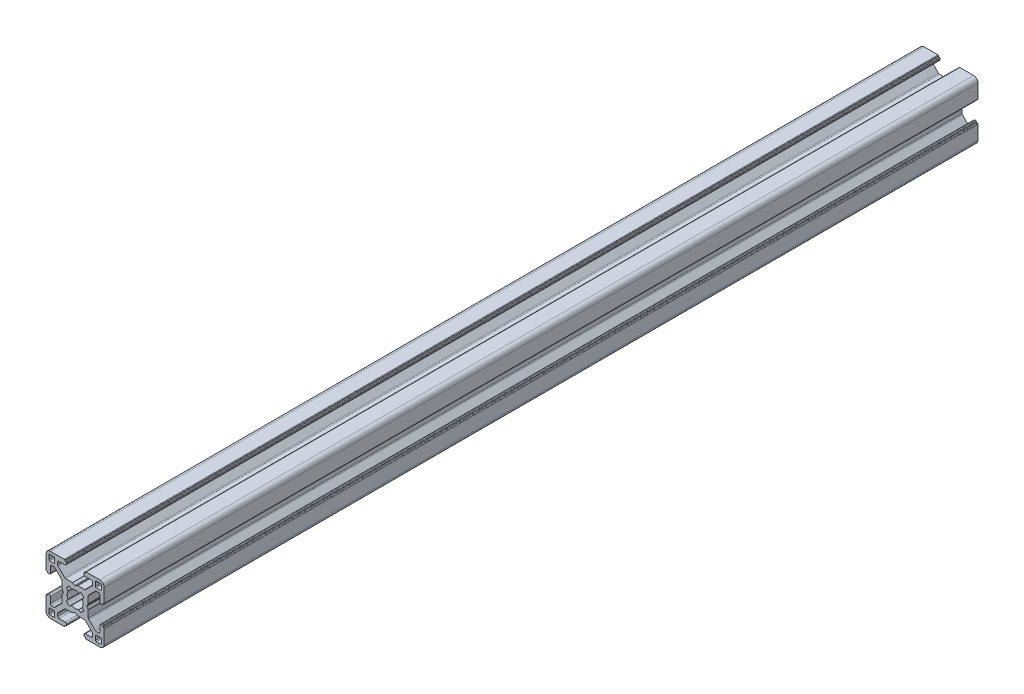
SolidWorks part; units mm, degrees
material "6063-O, Barra estrusa (SS)"
ref_plane "Piano frontale" through (0, 0, 0) normal (0, 0, 1) x (1, 0, 0)
ref_plane "Piano superiore" through (0, 0, 0) normal (0, 1, 0) x (1, 0, 0)
ref_plane "Piano destro" through (0, 0, 0) normal (1, 0, 0) x (0, 0, -1)
ref_plane "Piano1" through (0, 0, 100) normal (0, 0, 1) x (1, 0, 0)
sketch "Schizzo1" plane through (0, 0, 100) normal (0, 0, 1) x (1, 0, 0)
  line L0 (-1.9139, 2.9896) -> (-1.2582, 2.4453)
  line L1 (1.2582, 2.4453) -> (1.9139, 2.9896)
  line L2 (2.9922, 1.9099) -> (2.4453, 1.2582)
  line L3 (2.4453, -1.2582) -> (2.9922, -1.9099)
  line L4 (1.9139, -2.9896) -> (1.2582, -2.4453)
  line L5 (-1.2582, -2.4453) -> (-1.9139, -2.9896)
  line L6 (-2.9922, -1.9099) -> (-2.4453, -1.2582)
  line L7 (-2.4453, 1.2582) -> (-2.9922, 1.9099)
  line L8 (-9.3, 3) -> (-9, 3)
  line L9 (-8.5, 3.5) -> (-8.5, 5.5)
  line L10 (-8, 6) -> (-7.2678, 6)
  line L11 (-6.9142, 5.8536) -> (-4.6464, 3.5858)
  line L12 (-4.5, 3.2322) -> (-4.5, 0.9536)
  line L13 (-4.4732, 0.8536) -> (-4.0381, 0.1)
  line L14 (-4.0381, -0.1) -> (-4.4732, -0.8536)
  line L15 (-4.5, -0.9536) -> (-4.5, -3.2322)
  line L16 (-4.6464, -3.5858) -> (-6.9142, -5.8536)
  line L17 (-7.2678, -6) -> (-8, -6)
  line L18 (-8.5, -5.5) -> (-8.5, -3.5)
  line L19 (-9, -3) -> (-9.3, -3)
  line L20 (-9.5, -3.2) -> (-9.5, -3.35)
  line L21 (-9.7, -3.55) -> (-9.8, -3.55)
  line L22 (-10, -3.75) -> (-10, -8.5)
  line L23 (-8.5, -10) -> (-3.75, -10)
  line L24 (-3.55, -9.8) -> (-3.55, -9.7)
  line L25 (-3.35, -9.5) -> (-3.2, -9.5)
  line L26 (-3, -9.3) -> (-3, -9)
  line L27 (-3.5, -8.5) -> (-5.5, -8.5)
  line L28 (-6, -8) -> (-6, -7.2678)
  line L29 (-5.8536, -6.9142) -> (-3.5858, -4.6464)
  line L30 (-3.2322, -4.5) -> (-0.9536, -4.5)
  line L31 (-0.8536, -4.4732) -> (-0.1, -4.0381)
  line L32 (0.1, -4.0381) -> (0.8536, -4.4732)
  line L33 (0.9536, -4.5) -> (3.2322, -4.5)
  line L34 (3.5858, -4.6464) -> (5.8536, -6.9142)
  line L35 (6, -7.2678) -> (6, -8)
  line L36 (5.5, -8.5) -> (3.5, -8.5)
  line L37 (3, -9) -> (3, -9.3)
  line L38 (3.2, -9.5) -> (3.35, -9.5)
  line L39 (3.55, -9.7) -> (3.55, -9.8)
  line L40 (3.75, -10) -> (8.5, -10)
  line L41 (10, -8.5) -> (10, -3.75)
  line L42 (9.8, -3.55) -> (9.7, -3.55)
  line L43 (9.5, -3.35) -> (9.5, -3.2)
  line L44 (9.3, -3) -> (9, -3)
  line L45 (8.5, -3.5) -> (8.5, -5.5)
  line L46 (8, -6) -> (7.2678, -6)
  line L47 (6.9142, -5.8536) -> (4.6464, -3.5858)
  line L48 (4.5, -3.2322) -> (4.5, -0.9536)
  line L49 (4.4732, -0.8536) -> (4.0381, -0.1)
  line L50 (4.0381, 0.1) -> (4.4732, 0.8536)
  line L51 (4.5, 0.9536) -> (4.5, 3.2322)
  line L52 (4.6464, 3.5858) -> (6.9142, 5.8536)
  line L53 (7.2678, 6) -> (8, 6)
  line L54 (8.5, 5.5) -> (8.5, 3.5)
  line L55 (9, 3) -> (9.3, 3)
  line L56 (9.5, 3.2) -> (9.5, 3.35)
  line L57 (9.7, 3.55) -> (9.8, 3.55)
  line L58 (10, 3.75) -> (10, 8.5)
  line L59 (8.5, 10) -> (3.75, 10)
  line L60 (3.55, 9.8) -> (3.55, 9.7)
  line L61 (3.35, 9.5) -> (3.2, 9.5)
  line L62 (3, 9.3) -> (3, 9)
  line L63 (3.5, 8.5) -> (5.5, 8.5)
  line L64 (6, 8) -> (6, 7.2678)
  line L65 (5.8536, 6.9142) -> (3.5858, 4.6464)
  line L66 (3.2322, 4.5) -> (0.9536, 4.5)
  line L67 (0.8536, 4.4732) -> (0.1, 4.0381)
  line L68 (-0.1, 4.0381) -> (-0.8536, 4.4732)
  line L69 (-0.9536, 4.5) -> (-3.2322, 4.5)
  line L70 (-3.5858, 4.6464) -> (-5.8536, 6.9142)
  line L71 (-6, 7.2678) -> (-6, 8)
  line L72 (-5.5, 8.5) -> (-3.5, 8.5)
  line L73 (-3, 9) -> (-3, 9.3)
  line L74 (-3.2, 9.5) -> (-3.35, 9.5)
  line L75 (-3.55, 9.7) -> (-3.55, 9.8)
  line L76 (-3.75, 10) -> (-8.5, 10)
  line L77 (-10, 8.5) -> (-10, 3.75)
  line L78 (-9.8, 3.55) -> (-9.7, 3.55)
  line L79 (-9.5, 3.35) -> (-9.5, 3.2)
  line L80 (8.7, 7) -> (7.3, 7)
  line L81 (-7.3, 7) -> (-8.7, 7)
  line L82 (-7, 7.3) -> (-7, 8.7)
  line L83 (-7.3, 9) -> (-8.7, 9)
  line L84 (-9, 7.3) -> (-9, 8.7)
  line L85 (9, 7.3) -> (9, 8.7)
  line L86 (8.7, 9) -> (7.3, 9)
  line L87 (7, 7.3) -> (7, 8.7)
  line L88 (8.7, -9) -> (7.3, -9)
  line L89 (9, -8.7) -> (9, -7.3)
  line L90 (8.7, -7) -> (7.3, -7)
  line L91 (7, -8.7) -> (7, -7.3)
  line L92 (-7.3, -9) -> (-8.7, -9)
  line L93 (-7, -8.7) -> (-7, -7.3)
  line L94 (-7.3, -7) -> (-8.7, -7)
  line L95 (-9, -8.7) -> (-9, -7.3)
  arc A0 (-1.2582, 2.4453) -> (1.2582, 2.4453) centre (0, 0) cw
  arc A1 (1.9139, 2.9896) -> (2.9922, 1.9099) centre (0, 0) cw
  arc A2 (2.4453, 1.2582) -> (2.4453, -1.2582) centre (0, 0) cw
  arc A3 (2.9922, -1.9099) -> (1.9139, -2.9896) centre (0, 0) cw
  arc A4 (1.2582, -2.4453) -> (-1.2582, -2.4453) centre (0, 0) cw
  arc A5 (-1.9139, -2.9896) -> (-2.9922, -1.9099) centre (0, 0) cw
  arc A6 (-2.4453, -1.2582) -> (-2.4453, 1.2582) centre (0, 0) cw
  arc A7 (-2.9922, 1.9099) -> (-1.9139, 2.9896) centre (0, 0) cw
  arc A8 (-9.5, 3.2) -> (-9.3, 3) centre (-9.3, 3.2) ccw
  arc A9 (-9, 3) -> (-8.5, 3.5) centre (-9, 3.5) ccw
  arc A10 (-8.5, 5.5) -> (-8, 6) centre (-8, 5.5) cw
  arc A11 (-7.2678, 6) -> (-6.9142, 5.8536) centre (-7.2678, 5.5) cw
  arc A12 (-4.6464, 3.5858) -> (-4.5, 3.2322) centre (-5, 3.2322) cw
  arc A13 (-4.5, 0.9536) -> (-4.4732, 0.8536) centre (-4.3, 0.9536) ccw
  arc A14 (-4.0381, 0.1) -> (-4.0381, -0.1) centre (-4.2113, 0) cw
  arc A15 (-4.4732, -0.8536) -> (-4.5, -0.9536) centre (-4.3, -0.9536) ccw
  arc A16 (-4.5, -3.2322) -> (-4.6464, -3.5858) centre (-5, -3.2322) cw
  arc A17 (-6.9142, -5.8536) -> (-7.2678, -6) centre (-7.2678, -5.5) cw
  arc A18 (-8, -6) -> (-8.5, -5.5) centre (-8, -5.5) cw
  arc A19 (-8.5, -3.5) -> (-9, -3) centre (-9, -3.5) ccw
  arc A20 (-9.3, -3) -> (-9.5, -3.2) centre (-9.3, -3.2) ccw
  arc A21 (-9.5, -3.35) -> (-9.7, -3.55) centre (-9.7, -3.35) cw
  arc A22 (-9.8, -3.55) -> (-10, -3.75) centre (-9.8, -3.75) ccw
  arc A23 (-10, -8.5) -> (-8.5, -10) centre (-8.5, -8.5) ccw
  arc A24 (-3.75, -10) -> (-3.55, -9.8) centre (-3.75, -9.8) ccw
  arc A25 (-3.55, -9.7) -> (-3.35, -9.5) centre (-3.35, -9.7) cw
  arc A26 (-3.2, -9.5) -> (-3, -9.3) centre (-3.2, -9.3) ccw
  arc A27 (-3, -9) -> (-3.5, -8.5) centre (-3.5, -9) ccw
  arc A28 (-5.5, -8.5) -> (-6, -8) centre (-5.5, -8) cw
  arc A29 (-6, -7.2678) -> (-5.8536, -6.9142) centre (-5.5, -7.2678) cw
  arc A30 (-3.5858, -4.6464) -> (-3.2322, -4.5) centre (-3.2322, -5) cw
  arc A31 (-0.9536, -4.5) -> (-0.8536, -4.4732) centre (-0.9536, -4.3) ccw
  arc A32 (-0.1, -4.0381) -> (0.1, -4.0381) centre (0, -4.2113) cw
  arc A33 (0.8536, -4.4732) -> (0.9536, -4.5) centre (0.9536, -4.3) ccw
  arc A34 (3.2322, -4.5) -> (3.5858, -4.6464) centre (3.2322, -5) cw
  arc A35 (5.8536, -6.9142) -> (6, -7.2678) centre (5.5, -7.2678) cw
  arc A36 (6, -8) -> (5.5, -8.5) centre (5.5, -8) cw
  arc A37 (3.5, -8.5) -> (3, -9) centre (3.5, -9) ccw
  arc A38 (3, -9.3) -> (3.2, -9.5) centre (3.2, -9.3) ccw
  arc A39 (3.35, -9.5) -> (3.55, -9.7) centre (3.35, -9.7) cw
  arc A40 (3.55, -9.8) -> (3.75, -10) centre (3.75, -9.8) ccw
  arc A41 (8.5, -10) -> (10, -8.5) centre (8.5, -8.5) ccw
  arc A42 (10, -3.75) -> (9.8, -3.55) centre (9.8, -3.75) ccw
  arc A43 (9.7, -3.55) -> (9.5, -3.35) centre (9.7, -3.35) cw
  arc A44 (9.5, -3.2) -> (9.3, -3) centre (9.3, -3.2) ccw
  arc A45 (9, -3) -> (8.5, -3.5) centre (9, -3.5) ccw
  arc A46 (8.5, -5.5) -> (8, -6) centre (8, -5.5) cw
  arc A47 (7.2678, -6) -> (6.9142, -5.8536) centre (7.2678, -5.5) cw
  arc A48 (4.6464, -3.5858) -> (4.5, -3.2322) centre (5, -3.2322) cw
  arc A49 (4.5, -0.9536) -> (4.4732, -0.8536) centre (4.3, -0.9536) ccw
  arc A50 (4.0381, -0.1) -> (4.0381, 0.1) centre (4.2113, 0) cw
  arc A51 (4.4732, 0.8536) -> (4.5, 0.9536) centre (4.3, 0.9536) ccw
  arc A52 (4.5, 3.2322) -> (4.6464, 3.5858) centre (5, 3.2322) cw
  arc A53 (6.9142, 5.8536) -> (7.2678, 6) centre (7.2678, 5.5) cw
  arc A54 (8, 6) -> (8.5, 5.5) centre (8, 5.5) cw
  arc A55 (8.5, 3.5) -> (9, 3) centre (9, 3.5) ccw
  arc A56 (9.3, 3) -> (9.5, 3.2) centre (9.3, 3.2) ccw
  arc A57 (9.5, 3.35) -> (9.7, 3.55) centre (9.7, 3.35) cw
  arc A58 (9.8, 3.55) -> (10, 3.75) centre (9.8, 3.75) ccw
  arc A59 (10, 8.5) -> (8.5, 10) centre (8.5, 8.5) ccw
  arc A60 (3.75, 10) -> (3.55, 9.8) centre (3.75, 9.8) ccw
  arc A61 (3.55, 9.7) -> (3.35, 9.5) centre (3.35, 9.7) cw
  arc A62 (3.2, 9.5) -> (3, 9.3) centre (3.2, 9.3) ccw
  arc A63 (3, 9) -> (3.5, 8.5) centre (3.5, 9) ccw
  arc A64 (5.5, 8.5) -> (6, 8) centre (5.5, 8) cw
  arc A65 (6, 7.2678) -> (5.8536, 6.9142) centre (5.5, 7.2678) cw
  arc A66 (3.5858, 4.6464) -> (3.2322, 4.5) centre (3.2322, 5) cw
  arc A67 (0.9536, 4.5) -> (0.8536, 4.4732) centre (0.9536, 4.3) ccw
  arc A68 (0.1, 4.0381) -> (-0.1, 4.0381) centre (0, 4.2113) cw
  arc A69 (-0.8536, 4.4732) -> (-0.9536, 4.5) centre (-0.9536, 4.3) ccw
  arc A70 (-3.2322, 4.5) -> (-3.5858, 4.6464) centre (-3.2322, 5) cw
  arc A71 (-5.8536, 6.9142) -> (-6, 7.2678) centre (-5.5, 7.2678) cw
  arc A72 (-6, 8) -> (-5.5, 8.5) centre (-5.5, 8) cw
  arc A73 (-3.5, 8.5) -> (-3, 9) centre (-3.5, 9) ccw
  arc A74 (-3, 9.3) -> (-3.2, 9.5) centre (-3.2, 9.3) ccw
  arc A75 (-3.35, 9.5) -> (-3.55, 9.7) centre (-3.35, 9.7) cw
  arc A76 (-3.55, 9.8) -> (-3.75, 10) centre (-3.75, 9.8) ccw
  arc A77 (-8.5, 10) -> (-10, 8.5) centre (-8.5, 8.5) ccw
  arc A78 (-10, 3.75) -> (-9.8, 3.55) centre (-9.8, 3.75) ccw
  arc A79 (-9.7, 3.55) -> (-9.5, 3.35) centre (-9.7, 3.35) cw
  arc A80 (-8.7, 7) -> (-9, 7.3) centre (-8.7, 7.3) cw
  arc A81 (-7, 8.7) -> (-7.3, 9) centre (-7.3, 8.7) ccw
  arc A82 (-7.3, 7) -> (-7, 7.3) centre (-7.3, 7.3) ccw
  arc A83 (-8.7, 9) -> (-9, 8.7) centre (-8.7, 8.7) ccw
  arc A84 (7.3, 7) -> (7, 7.3) centre (7.3, 7.3) cw
  arc A85 (9, 8.7) -> (8.7, 9) centre (8.7, 8.7) ccw
  arc A86 (8.7, 7) -> (9, 7.3) centre (8.7, 7.3) ccw
  arc A87 (7.3, 9) -> (7, 8.7) centre (7.3, 8.7) ccw
  arc A88 (7.3, -9) -> (7, -8.7) centre (7.3, -8.7) cw
  arc A89 (9, -7.3) -> (8.7, -7) centre (8.7, -7.3) ccw
  arc A90 (8.7, -9) -> (9, -8.7) centre (8.7, -8.7) ccw
  arc A91 (7.3, -7) -> (7, -7.3) centre (7.3, -7.3) ccw
  arc A92 (-8.7, -9) -> (-9, -8.7) centre (-8.7, -8.7) cw
  arc A93 (-7, -7.3) -> (-7.3, -7) centre (-7.3, -7.3) ccw
  arc A94 (-7.3, -9) -> (-7, -8.7) centre (-7.3, -8.7) ccw
  arc A95 (-8.7, -7) -> (-9, -7.3) centre (-8.7, -7.3) ccw
  dimension "D1" = 0.3
  dimension "D2" = 1
  dimension "D3" = 1
  dimension "D4" = 1
  dimension "D7" = 1
  dimension "D8" = 1
  dimension "D9" = 1
  dimension "D10" = 1
  dimension "D5" = 2
  dimension "D6" = 2
extrude "Estrusione-Estrusione1" add sketch "Schizzo1" against normal blind 300
